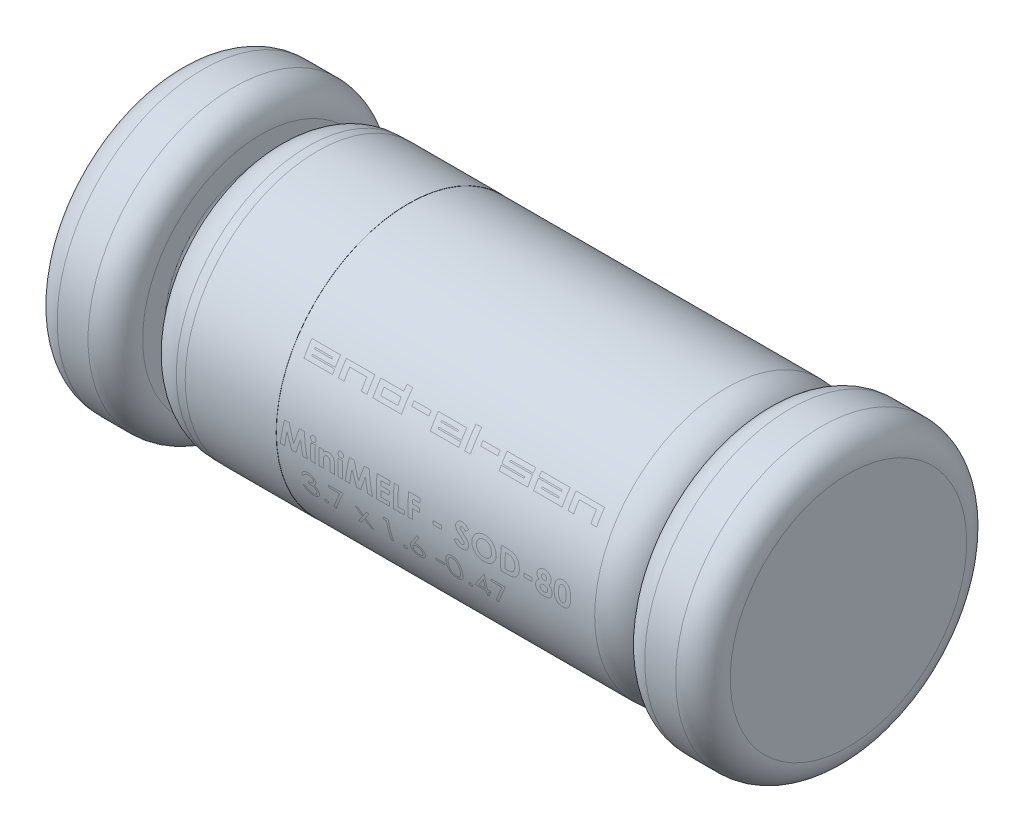
SolidWorks part; units mm, degrees
ref_plane "Ön Düzlem" through (0, 0, 0) normal (0, 0, 1) x (1, 0, 0)
ref_plane "Üst Düzlem" through (0, 0, 0) normal (0, 1, 0) x (1, 0, 0)
ref_plane "Sağ Düzlem" through (0, 0, 0) normal (1, 0, 0) x (0, 0, -1)
sketch "Çizim1" plane through (0, 0, 0) normal (1, 0, 0) x (0, 0, 1)
  circle A0 centre (0.8, 0) radius 0.8
  dimension "D1" = 1.6
sketch "Çizim2" plane through (0, 0, 0) normal (1, 0, 0) x (0, 0, -1)
  circle A2 centre (-0.8, 0) radius 0.725
  dimension "D2" = 1.45
extrude "Yükseklik-Ekstrüzyon3" add sketch "Çizim2" along normal mid plane 2.7
fillet "Radyus1" radius 0.2 2 edges at (-1.35, 0, 0.075) (1.35, 0, 0.075)
extrude "Ekstrüzyon-İnce1" add sketch "Çizim2<2>" against normal blind 0.5 from offset 0.6 thin offset against normal yes thin type one direction wall 0.001
sketch "Çizim2<2>" plane through (0, 0, 0) normal (1, 0, 0) x (0, 0, -1) same geometry as "Çizim2"
sketch "Çizim3" plane through (0, 0, 0) normal (-1, 0, 0) x (0, 0, 1)
  circle A2 centre (0.8, 0) radius 0.5
  dimension "D1" = 1
extrude "Yükseklik-Ekstrüzyon6" add sketch "Çizim3" along normal blind 0.06 from offset 1.35
extrude "Yükseklik-Ekstrüzyon2" add sketch "Çizim1" against normal blind 0.47 from offset 1.41 offset against normal yes
extrude "Yükseklik-Ekstrüzyon7" add sketch "Çizim1<3>" along normal blind 0.47 from offset 1.35
sketch "Çizim1<3>" plane through (0, 0, 0) normal (1, 0, 0) x (0, 0, 1) same geometry as "Çizim1"
fillet "Radyus2" radius 0.15 4 edges at (1.35, 0, 0) (1.82, 0, 0) (-1.41, 0, 0) (-1.88, 0, 0)
fillet "Radyus3" radius 0.03 1 edges at (-1.41, 0, 1.3)
ref_plane "Düzlem1" through (0, 0, 1) normal (0, 0, 1) x (1, 0, 0)
sketch "Çizim4" plane through (0, 0, 1) normal (0, 0, 1) x (1, 0, 0)
  line L0 (-0.5842, 0.3572) -> (1.1534, 0.3572) construction
  text T0 "end-el-san" font "Aerial" height 0.115
  text T1 "\r\n\r\n<b>MiniMELF - SOD-80</b>\r\n  3.7 x 1.6 -0.47\r\n" font "Century Gothic" height 0.12
wrap "Sar1" sketch "Çizim4" wrap type scribe source sketch "Çizim4" face at (-0.6, 0, 0.075)
